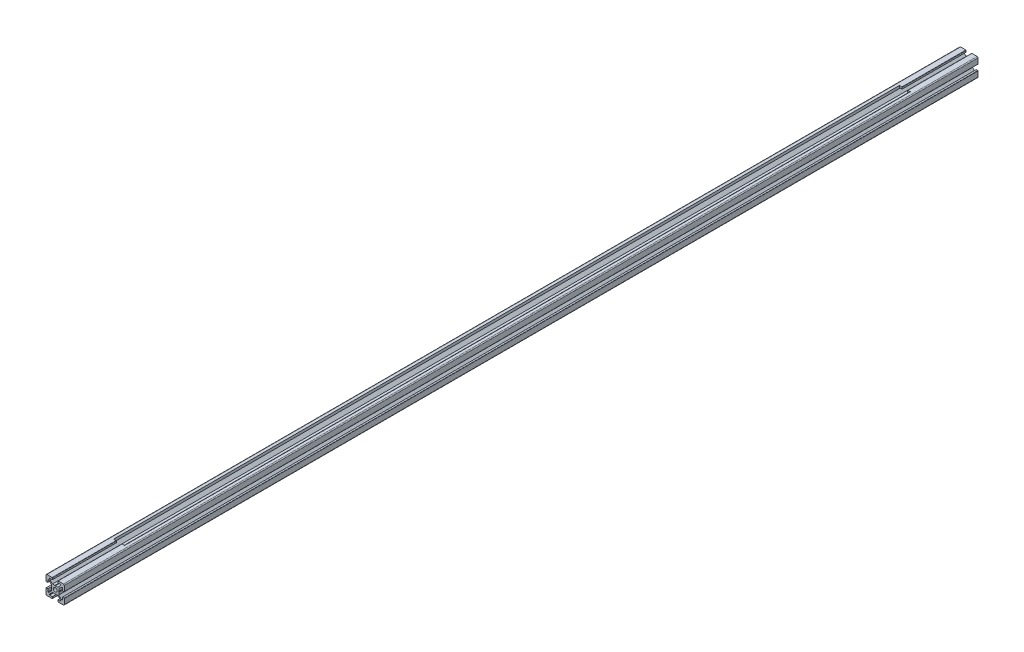
SolidWorks part; units mm, degrees
ref_plane "Front Plane" through (0, 0, 0) normal (0, 0, 1) x (1, 0, 0)
ref_plane "Top Plane" through (0, 0, 0) normal (0, 1, 0) x (1, 0, 0)
ref_plane "Right Plane" through (0, 0, 0) normal (1, 0, 0) x (0, 0, -1)
sketch "Sketch1" plane through (0, 0, 0) normal (0, 0, -1) x (-1, 0, 0)
  line L0 (10, 3.3) -> (10, 9)
  line L1 (9, 10) -> (3.3, 10)
  line L2 (3, 9.7) -> (3, 8)
  line L3 (3, 8) -> (6, 8)
  line L4 (6, 8) -> (6, 7.0607)
  line L5 (6, 7.0607) -> (2.9393, 4)
  line L6 (2.9393, 4) -> (0.3, 4)
  line L7 (0.3, 4) -> (0, 3.7)
  line L8 (0, 3.7) -> (-0.3, 4)
  line L9 (-0.3, 4) -> (-2.9393, 4)
  line L10 (-2.9393, 4) -> (-6, 7.0607)
  line L11 (-6, 7.0607) -> (-6, 8)
  line L12 (-6, 8) -> (-3, 8)
  line L13 (-3, 8) -> (-3, 9.7)
  line L14 (-3.3, 10) -> (-9, 10)
  line L15 (-10, 9) -> (-10, 3.3)
  line L16 (-9.7, 3) -> (-8, 3)
  line L17 (-8, 3) -> (-8, 6)
  line L18 (-8, 6) -> (-7.0607, 6)
  line L19 (-7.0607, 6) -> (-4, 2.9393)
  line L20 (-4, 2.9393) -> (-4, 0.3)
  line L21 (-4, 0.3) -> (-3.7, 0)
  line L22 (-3.7, 0) -> (-4, -0.3)
  line L23 (-4, -0.3) -> (-4, -2.9393)
  line L24 (-4, -2.9393) -> (-7.0607, -6)
  line L25 (-7.0607, -6) -> (-8, -6)
  line L26 (-8, -6) -> (-8, -3)
  line L27 (-8, -3) -> (-9.7, -3)
  line L28 (-10, -3.3) -> (-10, -9)
  line L29 (-9, -10) -> (-3.3, -10)
  line L30 (-3, -9.7) -> (-3, -8)
  line L31 (-3, -8) -> (-6, -8)
  line L32 (-6, -8) -> (-6, -7.0607)
  line L33 (-6, -7.0607) -> (-2.9393, -4)
  line L34 (-2.9393, -4) -> (-0.3, -4)
  line L35 (-0.3, -4) -> (0, -3.7)
  line L36 (0, -3.7) -> (0.3, -4)
  line L37 (0.3, -4) -> (2.9393, -4)
  line L38 (2.9393, -4) -> (6, -7.0607)
  line L39 (6, -7.0607) -> (6, -8)
  line L40 (6, -8) -> (3, -8)
  line L41 (3, -8) -> (3, -9.7)
  line L42 (3.3, -10) -> (9, -10)
  line L43 (10, -9) -> (10, -3.3)
  line L44 (9.7, -3) -> (8, -3)
  line L45 (8, -3) -> (8, -6)
  line L46 (8, -6) -> (7.0607, -6)
  line L47 (7.0607, -6) -> (4, -2.9393)
  line L48 (4, -2.9393) -> (4, -0.3)
  line L49 (4, -0.3) -> (3.7, 0)
  line L50 (3.7, 0) -> (4, 0.3)
  line L51 (4, 0.3) -> (4, 2.9393)
  line L52 (4, 2.9393) -> (7.0607, 6)
  line L53 (7.0607, 6) -> (8, 6)
  line L54 (8, 6) -> (8, 3)
  line L55 (8, 3) -> (9.7, 3)
  line L56 (9, -9) -> (-9, 9) construction
  line L57 (-9, -9) -> (9, 9) construction
  line L58 (-3.7, 0) -> (3.7, 0) construction
  line L59 (0, -3.7) -> (0, 3.7) construction
  circle A0 centre (0, 0) radius 2.1
  arc A1 (10, 9) -> (9, 10) centre (9, 9) ccw
  arc A2 (3.3, 10) -> (3, 9.7) centre (3.3, 9.7) ccw
  arc A3 (-3, 9.7) -> (-3.3, 10) centre (-3.3, 9.7) ccw
  arc A4 (-9, 10) -> (-10, 9) centre (-9, 9) ccw
  arc A5 (-10, 3.3) -> (-9.7, 3) centre (-9.7, 3.3) ccw
  arc A6 (-9.7, -3) -> (-10, -3.3) centre (-9.7, -3.3) ccw
  arc A7 (-10, -9) -> (-9, -10) centre (-9, -9) ccw
  arc A8 (-3.3, -10) -> (-3, -9.7) centre (-3.3, -9.7) ccw
  arc A9 (3, -9.7) -> (3.3, -10) centre (3.3, -9.7) ccw
  arc A10 (9, -10) -> (10, -9) centre (9, -9) ccw
  arc A11 (10, -3.3) -> (9.7, -3) centre (9.7, -3.3) ccw
  arc A12 (9.7, 3) -> (10, 3.3) centre (9.7, 3.3) ccw
  point P83 (0, 0)
  point P85 (0, 0)
  point P86 (0, 0)
  dimension "D1" = 1
  dimension "D4" = 0.3
  dimension "D10" = 4.2
  dimension "D2" = 20
  dimension "D3" = 6
  dimension "D5" = 3
  dimension "D6" = 1.7
  dimension "D7" = 0.9393
  dimension "D8" = 0.6
  dimension "D9" = 4
  dimension "D11" = 3.0607
  dimension "D12" = 3.0607
  dimension "D13" = 3.0607
  dimension "D14" = 5.7
  dimension "D15" = 5.7
  dimension "D16" = 0.9393
  dimension "D17" = 0.9393
  dimension "D18" = 3.0607
extrude "Boss-Extrude1" add sketch "Sketch1" against normal mid plane 1000
sketch "Sketch2" plane through (0, 0, 0) normal (0, 0, 1) x (1, 0, 0)
  line L0 (6, 8) -> (6, 10)
  line L1 (3.3, 10) -> (9, 10) construction
  line L2 (6, 10) -> (-6, 10)
  line L3 (-9, 10) -> (-3.3, 10) construction
  line L4 (-6, 10) -> (-6, 8)
  line L5 (-3, 8) -> (-6, 8) construction
  line L6 (-6, 8) -> (-6, 7.0607) construction
  line L7 (6, 8) -> (-6, 8)
  line L8 (6, 7.0607) -> (6, 8) construction
extrude "Cut-Extrude1" cut sketch "Sketch2" against normal offset from surface 70 and the other way offset from surface 70 up to face at (2.1, 0, -500) other way up to face at (2.1, 0, 500)
ref_axis "Axis1" through (0, 0, 500) along (0, 0, -1)
pattern_circular "CirPattern1" [suppressed] count 4 over 360 about axis through (0, 0, 500) along (0, 0, -1) of bodies 104
mirror "Mirror1" about plane through (0, 0, 0) normal (0, 1, 0) of "Cut-Extrude1"
